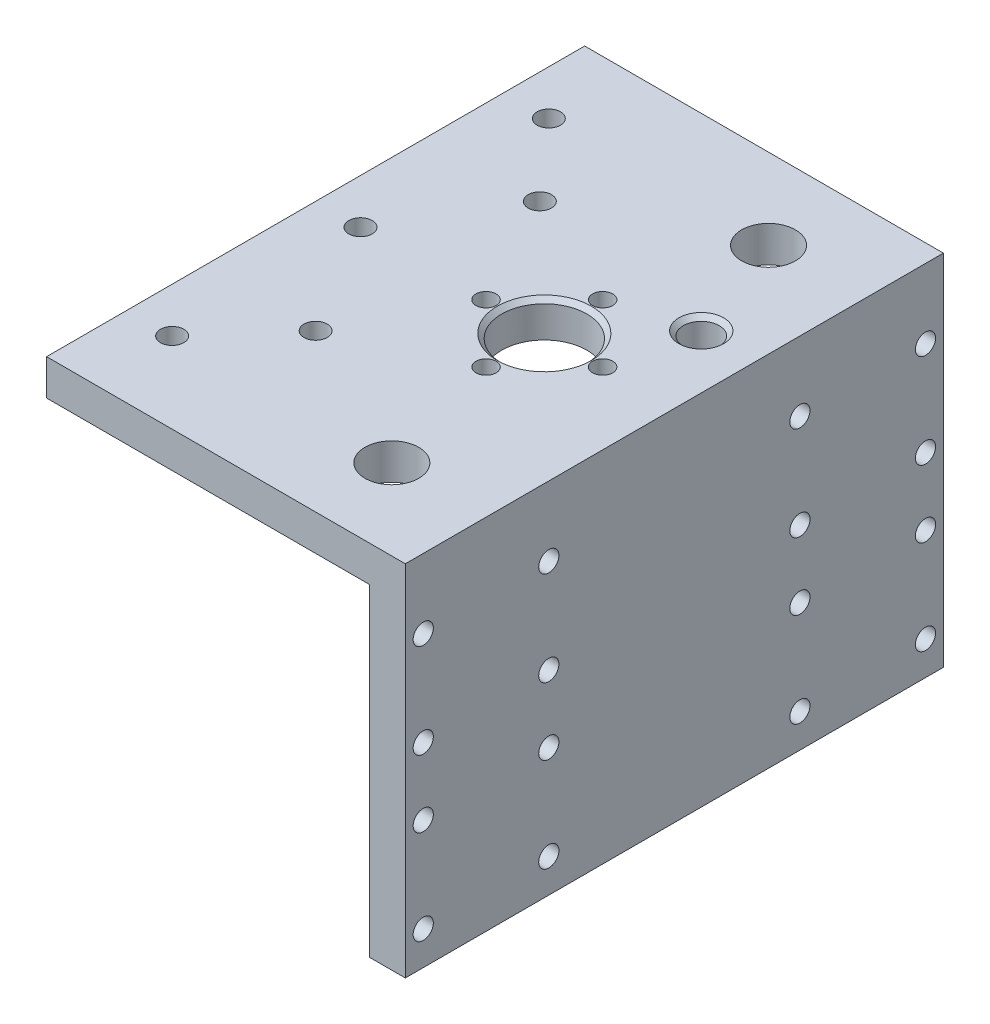
SolidWorks part; units mm, degrees
material "Lega 1060"
ref_plane "Piano frontale" through (0, 0, 0) normal (0, 0, 1) x (1, 0, 0)
ref_plane "Piano superiore" through (0, 0, 0) normal (0, 1, 0) x (1, 0, 0)
ref_plane "Piano destro" through (0, 0, 0) normal (1, 0, 0) x (0, 0, -1)
sketch "Schizzo1" plane through (0, 0, 0) normal (0, 0, 1) x (1, 0, 0)
  line L0 (0, 0) -> (-80, 0)
  line L1 (-80, 0) -> (-80, -8)
  line L2 (-80, -8) -> (-8, -8)
  line L3 (-8, -8) -> (-8, -80)
  line L4 (-8, -80) -> (0, -80)
  line L5 (0, -80) -> (0, 0)
  dimension "D1" = 80
  dimension "D2" = 80
  dimension "D3" = 8
  dimension "D4" = 8
extrude "Estrusione-Estrusione1" add sketch "Schizzo1" along normal blind 120
sketch "Schizzo12" plane through (0, 0, 0) normal (1, 0, 0) x (0, 0, -1)
  line L0 (-60, 0) -> (-60, -80) construction
  line L1 (-120, 0) -> (0, 0) construction
  line L2 (-120, -80) -> (0, -80) construction
  line L3 (-18, -24) -> (-18, 0) construction
  line L4 (-102, -24) -> (-102, 0) construction
  line L5 (-102, -62) -> (-18, -62) construction
  line L8 (-18, -26) -> (-102, -26) construction
  circle A0 centre (-116, -15.5) radius 2.25
  circle A1 centre (-88, -15.5) radius 2.25
  circle A2 centre (-88, -36.5) radius 2.25
  circle A3 centre (-116, -36.5) radius 2.25
  circle A4 centre (-32, -36.5) radius 2.25
  circle A5 centre (-4, -36.5) radius 2.25
  circle A6 centre (-32, -15.5) radius 2.25
  circle A7 centre (-4, -15.5) radius 2.25
  circle A8 centre (-116, -51.5) radius 2.25
  circle A9 centre (-88, -51.5) radius 2.25
  circle A10 centre (-88, -72.5) radius 2.25
  circle A11 centre (-116, -72.5) radius 2.25
  circle A12 centre (-4, -72.5) radius 2.25
  circle A13 centre (-32, -72.5) radius 2.25
  circle A14 centre (-32, -51.5) radius 2.25
  circle A15 centre (-4, -51.5) radius 2.25
  dimension "D1" = 4.5
  dimension "D5" = 4.5
  dimension "D2" = 14
  dimension "D3" = 10.5
  dimension "D4" = 36
  dimension "D6" = 14
  dimension "D7" = 10.5
  dimension "D8" = 26
  dimension "D9" = 18
sketch "Schizzo6" plane through (0, 0, 0) normal (0, 1, 0) x (1, 0, 0)
  line L0 (-21, -0.5808) -> (-21, -110.5835) construction
  line L2 (0, 0) -> (-80, 0) construction
  line L3 (-32.5218, -60) -> (-8.0464, -60) construction
  line L6 (0, -120) -> (-80, -120) construction
  circle A0 centre (-21, -18) radius 6
  circle A1 centre (-21, -102) radius 6
  dimension "D2" = 12
  dimension "D1" = 13
  dimension "D3" = 18
extrude "Taglio-Estrusione2" cut sketch "Schizzo6" against normal up to next
sketch "Schizzo7" plane through (0, 0, 0) normal (0, 1, 0) x (1, 0, 0)
  line L0 (-53.636, -60) -> (3.6289, -60) construction
  line L1 (0, -120) -> (-80, -120) construction
  line L2 (0, 0) -> (-80, 0) construction
  line L3 (-21, -18) -> (-21, -102) construction
  line L4 (0, -120) -> (0, 0) construction
  circle A0 centre (-29, -60) radius 9.5
  circle A1 centre (-12, -42) radius 4
  point P18 (-11.3573, 0)
  dimension "D1" = 19
  dimension "D2" = 8
  dimension "D3" = 8
  dimension "D4" = 12
  dimension "D5" = 42
extrude "Taglio-Estrusione3" cut sketch "Schizzo7" against normal up to next
hole_wizard "Foro per Vite M4-2" positions "Schizzo9" profile "Schizzo8" hole size "M4" standard "ISO" end condition through all
sketch "Schizzo9" plane through (0, 0, 0) normal (0, 1, 0) x (1, 0, 0)
  line L0 (-18.4657, -60) -> (-16, -60) construction
  line L2 (-29, -57.7684) -> (-29, -66.5063) construction
  circle A2 centre (-29, -60) radius 9.5 construction
  point P0 (-29, -47)
  point P2 (-42, -60)
  point P4 (-29, -73)
  point P8 (-16, -60)
  point P20 (-29, -60)
  dimension "D1" = 26
  dimension "D2" = 13
  dimension "D3" = 13
sketch "Schizzo8" plane through (-29, 0, 47) normal (1, 0, 0) x (0, 0, 1)
  line L0 (0, 0) -> (0, 80)
  line L1 (0, 80) -> (2.25, 80)
  line L2 (2.25, 80) -> (2.25, 0)
  line L5 (2.25, 0) -> (0, 0)
  line L11 (0, -6.35) -> (0, 107.95) construction
  dimension "Thru Hole Dia." = 4.5
  dimension "Thru Hole Depth" = 80
extrude "Taglio-Estrusione4" cut sketch "Schizzo12" against normal blind 10
sketch "Schizzo14" plane through (0, 0, 0) normal (0, 1, 0) x (1, 0, 0)
  line L0 (-70, 0) -> (-70, -120) construction
  line L1 (0, 0) -> (-80, 0) construction
  line L2 (0, -120) -> (-80, -120) construction
  line L3 (-80, -120) -> (-80, 0) construction
  line L4 (-55, 0) -> (-55, -120) construction
  line L5 (-21, -102) -> (-80, -102) construction
  line L6 (-80, -60) -> (0, -60) construction
  line L7 (0, -120) -> (0, 0) construction
  line L8 (-21, -18) -> (-80, -18) construction
  circle A0 centre (-70, -18) radius 2.6
  circle A1 centre (-70, -60) radius 2.6
  circle A2 centre (-70, -102) radius 2.6
  circle A3 centre (-55, -35) radius 2.6
  circle A4 centre (-55, -85) radius 2.6
  dimension "D3" = 5.2
  dimension "D4" = 5.2
  dimension "D5" = 5.2
  dimension "D6" = 5.2
  dimension "D7" = 5.2
  dimension "D1" = 10
  dimension "D2" = 25
  dimension "D8" = 35
  dimension "D9" = 35
extrude "Taglio-Estrusione5" cut sketch "Schizzo14" against normal blind 10
chamfer "Smusso1" distance 1 angle 45 1 edges at (-16, 0, 42)
chamfer "Smusso2" distance 1 angle 45 1 edges at (-38.5, 0, 60)
